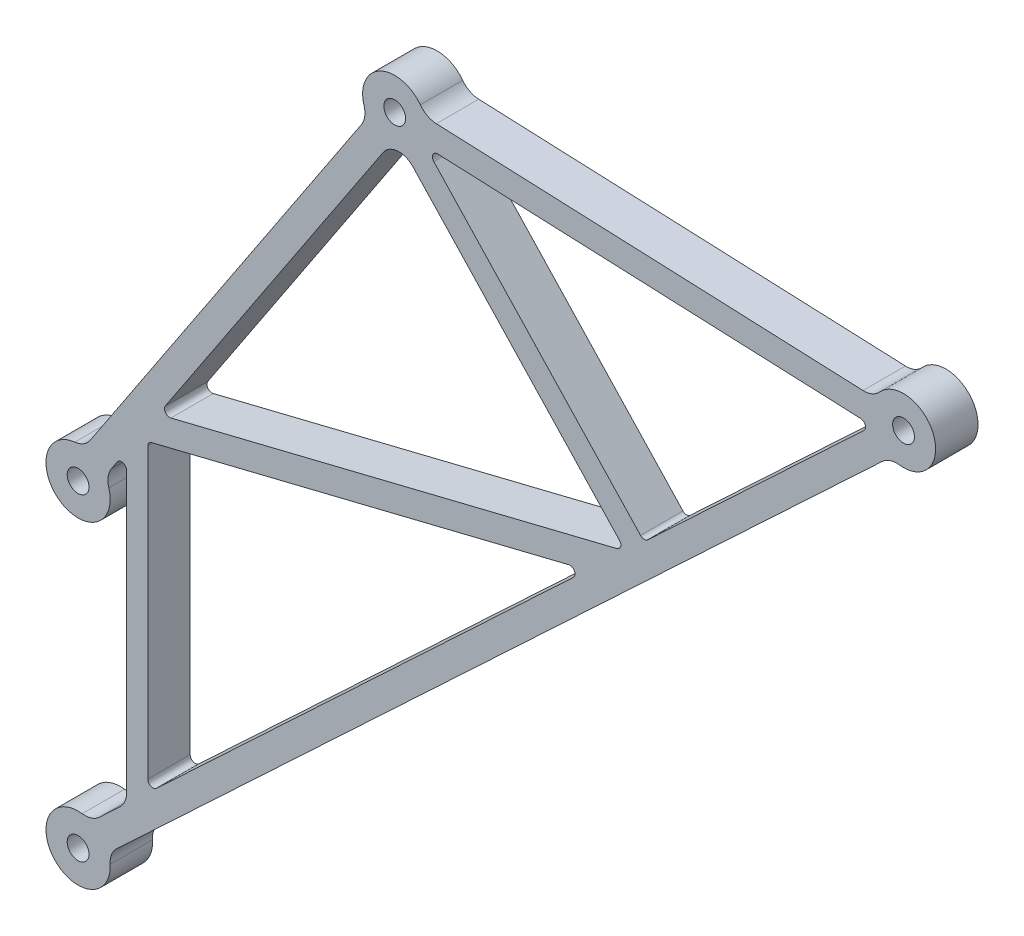
SolidWorks part; units mm, degrees
material "7075-T6 (SN)"
ref_plane "Front Plane" through (0, 0, 0) normal (0, 0, 1) x (1, 0, 0)
ref_plane "Top Plane" through (0, 0, 0) normal (0, 1, 0) x (1, 0, 0)
ref_plane "Right Plane" through (0, 0, 0) normal (1, 0, 0) x (0, 0, -1)
sketch "Sketch1" plane through (0, 0, 0) normal (0, 0, 1) x (1, 0, 0)
  line L0 (1568.1065, -30.7834) -> (1473.2701, -173.7947) construction
  line L1 (1473.2701, -269.0447) -> (1473.2701, -173.7947) construction
  line L2 (1568.1065, -30.7834) -> (1720.5045, -37.1188) construction
  line L3 (1568.1065, -28.0402) -> (1720.5045, -34.3756) construction
  line L4 (1720.5045, -37.1188) -> (1473.2701, -269.0447) construction
  line L5 (1720.5045, -34.3756) -> (1720.5045, -37.1188) construction
  line L6 (1568.1065, -28.0402) -> (1568.1065, -30.7834) construction
  line L7 (1570.0946, -34.6794) -> (1476.4454, -175.9004)
  line L8 (1487.7958, -242.2366) -> (1487.7958, -169.286)
  line L10 (1466.6926, -262.0331) -> (1487.7958, -242.2366)
  line L11 (1481.2824, -179.108) -> (1487.7958, -169.286)
  line L12 (1494.1458, -244.2377) -> (1494.1458, -149.2086)
  line L13 (1570.0946, -34.6794) -> (1711.2795, -40.5486)
  line L14 (1711.2795, -40.5486) -> (1470.6635, -266.266)
  line L15 (1566.1185, -26.8875) -> (1470.0949, -171.6891)
  line L16 (1566.1185, -26.8875) -> (1729.7295, -33.689)
  line L17 (1729.7295, -33.689) -> (1475.8768, -271.8235)
  line L18 (1487.7958, -242.2366) -> (1487.7958, -250.1945)
  line L19 (1487.7958, -169.286) -> (1487.7958, -158.7843)
  line L20 (1568.1065, -30.7834) -> (1644.4503, -112.1663) construction
  line L21 (1644.4503, -112.1663) -> (1494.1458, -149.2086) construction
  line L22 (1571.3668, -39.8276) -> (1637.2174, -110.0248)
  line L23 (1637.2174, -110.0248) -> (1497.2563, -144.518)
  line L24 (1577.2649, -34.9774) -> (1642.7749, -104.8115)
  line L25 (1625.8704, -120.6693) -> (1494.1458, -153.1326)
  line L26 (1637.2174, -110.0248) -> (1493.2341, -145.5093) construction
  line L27 (1565.3278, -33.3901) -> (1637.2174, -110.0248) construction
  circle A4 centre (1568.1065, -28.0402) radius 3.2639 construction
  circle A5 centre (1720.5045, -34.3756) radius 3.2639 construction
  circle A6 centre (1473.2701, -173.7947) radius 3.2639
  circle A7 centre (1473.2701, -269.0447) radius 3.2639
  circle A8 centre (1473.2701, -269.0447) radius 9.6139
  circle A9 centre (1473.2701, -173.7947) radius 9.6139
  circle A10 centre (1568.1065, -28.0402) radius 9.6139 construction
  circle A11 centre (1720.5045, -34.3756) radius 9.6139 construction
  circle A12 centre (1568.1065, -30.7834) radius 3.2639
  circle A13 centre (1720.5045, -37.1188) radius 3.2639
  circle A14 centre (1568.1065, -30.7834) radius 9.6139
  circle A15 centre (1720.5045, -37.1188) radius 9.6139
  point P51 (0, 0)
  point P52 (0, 0)
  point P53 (0, 0)
  dimension "D4" = 6.5278
  dimension "D5" = 19.2278
  dimension "D3" = 72.9506
  dimension "D6" = 2.7432
  dimension "D7" = 2.7432
  dimension "D10" = 6.35
  dimension "D12" = 3.81
  dimension "D13" = 3.81
  dimension "D1" = 6.35
  dimension "D8" = 3.81
  dimension "D9" = 3.81
  dimension "D11" = 3.81
extrude "Boss-Extrude1" add sketch "Sketch1" along normal mid plane 12.7
fillet "Fillet1" radius 6.35 9 edges at (1477.101, -260.227, 0) (1482.3144, -265.7845, 0) (1481.3236, -168.5441, 0) (1474.9731, -164.3329, 0) (1577.0839, -27.3433, 0) (1560.0531, -36.034, 0) (1711.8437, -32.9454, 0) (1716.6737, -45.9364, 0) (1487.7958, -250.1945, 0)
fillet "Fillet2" radius 1.524 9 edges at (1487.7958, -158.7843, 0) (1497.2563, -144.518, 0) (1494.1458, -153.1326, 0) (1494.1458, -244.2377, 0) (1625.8704, -120.6693, 0) (1637.2174, -110.0248, 0) (1642.7749, -104.8115, 0) (1577.2649, -34.9774, 0) (1711.2795, -40.5486, 0)
fillet "Fillet3" radius 5.715 4 edges at (1568.9127, -40.3635, -6.35) (1571.3668, -39.8276, 0) (1566.4036, -40.2453, 0) (1568.9127, -40.3635, 6.35)
